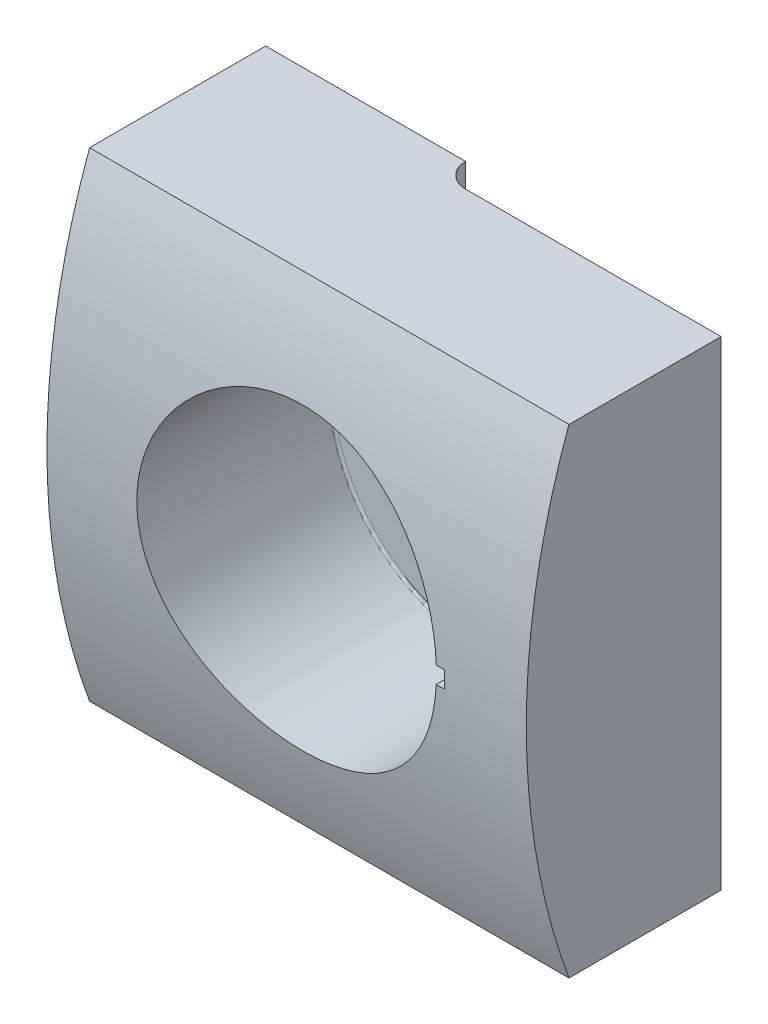
SolidWorks part; units mm, degrees
other "Markup1"
sketch "Sketch6" plane through (50.8, 0, 20.6375) normal (0.2696, -0.6554, 0.7056) x (-0.5737, -0.6978, -0.4289)
material "ABS"
ref_plane "Front Plane" through (0, 0, 0) normal (0, 0, 1) x (1, 0, 0)
ref_plane "Top Plane" through (0, 0, 0) normal (0, 1, 0) x (1, 0, 0)
ref_plane "Right Plane" through (0, 0, 0) normal (1, 0, 0) x (0, 0, -1)
sketch "Sketch1" plane through (0, 0, 0) normal (0, 0, 1) x (1, 0, 0)
  line L6 (0, 0) -> (50.8, 0)
  line L7 (0, 0) -> (0, 50.8)
  line L8 (0, 50.8) -> (50.8, 50.8)
  line L9 (50.8, 0) -> (50.8, 50.8)
  circle A1 centre (25.4, 25.4) radius 15.875
  point P9 (25.4, 50.8)
  point P12 (50.8, 25.4)
  dimension "D1" = 31.75
  dimension "D2" = 50.8
  dimension "D3" = 50.8
extrude "Boss-Extrude1" add sketch "Sketch1" along normal blind 20.6375
sketch "Sketch3" plane through (0, 0, 0) normal (-1, 0, 0) x (0, 0, 1)
  line L6 (16.1196, 50.8) -> (20.6375, 50.8)
  line L7 (16.1196, 50.8) -> (20.6375, 50.8)
  line L8 (20.6375, 0) -> (16.1196, 0)
  line L11 (20.6375, 0) -> (20.6375, 50.8)
  arc A1 (16.1196, 0) -> (16.1196, 50.8) centre (-53.0225, 25.4) ccw
  line M4 (0, 0) -> (20.6375, 0)
  line M5 (20.6375, 0) -> (20.6375, 50.8)
  line M6 (20.6375, 50.8) -> (0, 50.8)
  dimension "D1" = 73.66
extrude "Cut-Extrude1" cut sketch "Sketch3" against normal through all contours M6 | M5 M4 region at (0, 6.3104, 19.2896) region at (0, 44.4896, 19.2896)
sketch "Sketch4" plane through (0, 0, 0) normal (0, 0, -1) x (-1, 0, 0)
  line L1 (-38.2926, 26.1976) -> (-42.1074, 26.1976)
  line L2 (-38.2926, 26.1976) -> (-38.2926, 24.4196)
  line L3 (-38.2926, 24.4196) -> (-42.1074, 24.4196)
  line L4 (-42.1074, 26.1976) -> (-42.1074, 24.4196)
  dimension "D1" = 1.778
extrude "Cut-Extrude2" cut sketch "Sketch4" against normal through all
sketch "Sketch5" plane through (0, 0, 0) normal (0, 0, -1) x (-1, 0, 0)
  line L1 (-21.1931, 50.8) -> (0, 50.8)
  line L2 (-21.1931, 50.8) -> (-21.1931, 0)
  line L3 (-21.1931, 0) -> (0, 0)
  line L4 (0, 50.8) -> (0, 0)
  line L5 (0, 50.8) -> (0, 0) construction
  line L6 (0, 0) -> (-50.8, 0) construction
  line L7 (-50.8, 50.8) -> (0, 50.8) construction
  circle A2 centre (-25.4, 25.4) radius 11.7075 construction
extrude "Boss-Extrude2" add sketch "Sketch5" along normal blind 2.54
fillet "Fillet1" radius 2.54 2 edges at (21.1931, 45.7537, 0) (21.1931, 5.0463, 0)
fillet "Fillet2" radius 2.54 2 edges at (21.1931, 10.0926, -1.27) (21.1931, 40.7074, -1.27)
fillet "Fillet3" radius 0.254 1 edges at (9.525, 25.4, 0)
